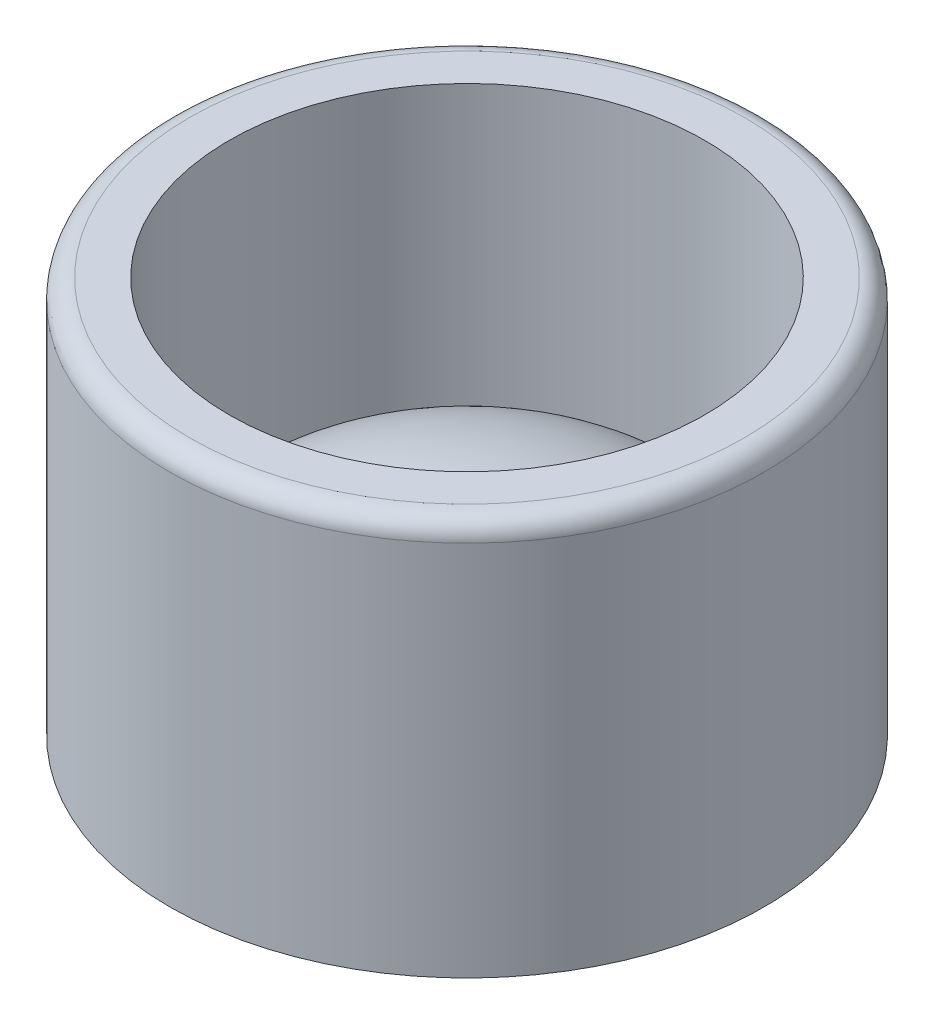
SolidWorks part; units mm, degrees
material "1060 Alloy"
ref_plane "Front Plane" through (0, 0, 0) normal (0, 0, 1) x (1, 0, 0)
ref_plane "Top Plane" through (0, 0, 0) normal (0, 1, 0) x (1, 0, 0)
ref_plane "Right Plane" through (0, 0, 0) normal (1, 0, 0) x (0, 0, -1)
sketch "Sketch2" plane through (0, 0, 0) normal (0, 1, 0) x (1, 0, 0)
  circle A0 centre (0, 0) radius 7.5
  dimension "D1" = 15
extrude "Boss-Extrude1" add sketch "Sketch2" along normal blind 10
sketch "Sketch3" plane through (0, 10, 0) normal (0, 1, 0) x (1, 0, 0)
  circle A0 centre (0, 0) radius 6
extrude "Cut-Extrude1" cut sketch "Sketch3" against normal blind 8
dome "Dome1" faces to dome 1 distance 3 reverse direction no elliptical dome yes face at (0, 2, 6) parameters "D1"=3
fillet "Fillet1" radius 0.5 1 edges at (0, 10, 7.5)
